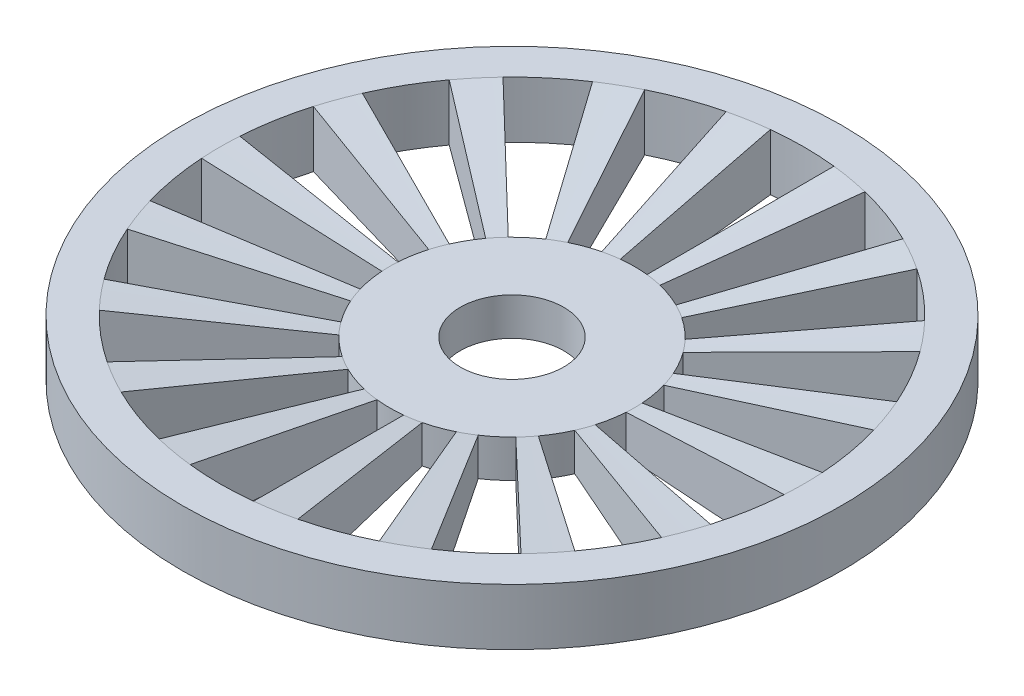
SolidWorks part; units mm, degrees
ref_plane "Front Plane" through (0, 0, 0) normal (0, 0, 1) x (1, 0, 0)
ref_plane "Top Plane" through (0, 0, 0) normal (0, 1, 0) x (1, 0, 0)
ref_plane "Right Plane" through (0, 0, 0) normal (1, 0, 0) x (0, 0, -1)
ref_plane "Plane1" through (0, 3, 0) normal (0, 1, 0) x (1, 0, 0)
sketch "Sketch1" plane through (0, 0, 0) normal (0, 1, 0) x (1, 0, 0)
  circle A0 centre (0, 0) radius 15.5
  circle A1 centre (0, 0) radius 17.5
  point P17 (14.8721, 4.3669)
  point P26 (13.0394, 8.3799)
  point P27 (10.1503, 11.7141)
  point P28 (6.4389, 14.0993)
  point P29 (2.2059, 15.3422)
  point P30 (-2.2059, 15.3422)
  point P31 (-6.4389, 14.0993)
  point P32 (-10.1503, 11.7141)
  point P33 (-13.0394, 8.3799)
  point P34 (-14.8721, 4.3669)
  point P35 (-15.5, 0)
  point P36 (-14.8721, -4.3669)
  point P37 (-13.0394, -8.3799)
  point P38 (-10.1503, -11.7141)
  point P39 (-6.4389, -14.0993)
  point P40 (-2.2059, -15.3422)
  point P41 (2.2059, -15.3422)
  point P42 (6.4389, -14.0993)
  point P43 (10.1503, -11.7141)
  point P44 (13.0394, -8.3799)
  point P45 (14.8721, -4.3669)
  point P46 (15.5, 0)
  dimension "D1" = 35
  dimension "D2" = 2
sketch "Sketch2" plane through (0, 0, 0) normal (0, 1, 0) x (1, 0, 0)
  circle A0 centre (0, 0) radius 6.5
  dimension "D1" = 13
sketch "Sketch4" plane through (0, 0, 0) normal (0, 1, 0) x (1, 0, 0)
  line L0 (0, 6.5) -> (0, 17.5) construction
  line L3 (1.1287, 6.4013) -> (3.0388, 17.2341) construction
  line L4 (2.2231, 6.108) -> (5.9854, 16.4446) construction
  line L5 (3.25, 5.6292) -> (8.75, 15.1554) construction
  line L6 (4.1781, 4.9793) -> (11.2488, 13.4058) construction
  line L7 (4.9793, 4.1781) -> (13.4058, 11.2488) construction
  line L8 (5.6292, 3.25) -> (15.1554, 8.75) construction
  line L9 (6.108, 2.2231) -> (16.4446, 5.9854) construction
  line L10 (6.4013, 1.1287) -> (17.2341, 3.0388) construction
  line L11 (6.5, 0) -> (17.5, 0) construction
  line L12 (6.4013, -1.1287) -> (17.2341, -3.0388) construction
  line L13 (6.108, -2.2231) -> (16.4446, -5.9854) construction
  line L14 (5.6292, -3.25) -> (15.1554, -8.75) construction
  line L15 (4.9793, -4.1781) -> (13.4058, -11.2488) construction
  line L16 (4.1781, -4.9793) -> (11.2488, -13.4058) construction
  line L17 (3.25, -5.6292) -> (8.75, -15.1554) construction
  line L18 (2.2231, -6.108) -> (5.9854, -16.4446) construction
  line L19 (1.1287, -6.4013) -> (3.0388, -17.2341) construction
  line L20 (0, -6.5) -> (0, -17.5) construction
  line L21 (-1.1287, -6.4013) -> (-3.0388, -17.2341) construction
  line L22 (-2.2231, -6.108) -> (-5.9854, -16.4446) construction
  line L23 (-3.25, -5.6292) -> (-8.75, -15.1554) construction
  line L24 (-4.1781, -4.9793) -> (-11.2488, -13.4058) construction
  line L25 (-4.9793, -4.1781) -> (-13.4058, -11.2488) construction
  line L26 (-5.6292, -3.25) -> (-15.1554, -8.75) construction
  line L27 (-6.108, -2.2231) -> (-16.4446, -5.9854) construction
  line L28 (-6.4013, -1.1287) -> (-17.2341, -3.0388) construction
  line L29 (-6.5, 0) -> (-17.5, 0) construction
  line L30 (-6.4013, 1.1287) -> (-17.2341, 3.0388) construction
  line L31 (-6.108, 2.2231) -> (-16.4446, 5.9854) construction
  line L32 (-5.6292, 3.25) -> (-15.1554, 8.75) construction
  line L33 (-4.9793, 4.1781) -> (-13.4058, 11.2488) construction
  line L34 (-4.1781, 4.9793) -> (-11.2488, 13.4058) construction
  line L35 (-3.25, 5.6292) -> (-8.75, 15.1554) construction
  line L36 (-2.2231, 6.108) -> (-5.9854, 16.4446) construction
  line L37 (-1.1287, 6.4013) -> (-3.0388, 17.2341) construction
  line L39 (0.7076, 6.4614) -> (1.9052, 17.396)
  line L42 (1.545, 6.3137) -> (4.1595, 16.9985)
  line L43 (2.8749, 5.8297) -> (7.7401, 15.6953)
  line L44 (3.6112, 5.4046) -> (9.7225, 14.5507)
  line L45 (4.6954, 4.4948) -> (12.6414, 12.1015)
  line L46 (5.2419, 3.8435) -> (14.1128, 10.3479)
  line L47 (5.9495, 2.6179) -> (16.018, 7.0481)
  line L48 (6.2403, 1.8189) -> (16.8009, 4.897)
  line L49 (6.4861, 0.4251) -> (17.4625, 1.1446)
  line L50 (6.4861, -0.4251) -> (17.4625, -1.1446)
  line L51 (6.2403, -1.8189) -> (16.8009, -4.897)
  line L52 (5.9495, -2.6179) -> (16.018, -7.0481)
  line L53 (5.2419, -3.8435) -> (14.1128, -10.3479)
  line L54 (4.6954, -4.4948) -> (12.6414, -12.1015)
  line L55 (3.6112, -5.4046) -> (9.7225, -14.5507)
  line L56 (2.8749, -5.8297) -> (7.7401, -15.6953)
  line L57 (1.545, -6.3137) -> (4.1595, -16.9985)
  line L58 (0.7076, -6.4614) -> (1.9052, -17.396)
  line L59 (-0.7076, -6.4614) -> (-1.9052, -17.396)
  line L60 (-1.545, -6.3137) -> (-4.1595, -16.9985)
  line L61 (-2.8749, -5.8297) -> (-7.7401, -15.6953)
  line L62 (-3.6112, -5.4046) -> (-9.7225, -14.5507)
  line L63 (-4.6954, -4.4948) -> (-12.6414, -12.1015)
  line L64 (-5.2419, -3.8435) -> (-14.1128, -10.3479)
  line L65 (-5.9495, -2.6179) -> (-16.018, -7.0481)
  line L66 (-6.2403, -1.8189) -> (-16.8009, -4.897)
  line L67 (-6.4861, -0.4251) -> (-17.4625, -1.1446)
  line L68 (-6.4861, 0.4251) -> (-17.4625, 1.1446)
  line L69 (-6.2403, 1.8189) -> (-16.8009, 4.897)
  line L70 (-5.9495, 2.6179) -> (-16.018, 7.0481)
  line L71 (-5.2419, 3.8435) -> (-14.1128, 10.3479)
  line L72 (-4.6954, 4.4948) -> (-12.6414, 12.1015)
  line L73 (-3.6112, 5.4046) -> (-9.7225, 14.5507)
  line L74 (-2.8749, 5.8297) -> (-7.7401, 15.6953)
  line L75 (-1.545, 6.3137) -> (-4.1595, 16.9985)
  line L76 (-0.7076, 6.4614) -> (-1.9052, 17.396)
  circle A86 centre (0, 0) radius 6.5 construction
  circle A90 centre (0, 0) radius 17.5 construction
  arc A91 (0.7076, 6.4614) -> (1.545, 6.3137) centre (0, 0) cw
  arc A92 (4.1595, 16.9985) -> (1.9052, 17.396) centre (0, 0) ccw
  arc A93 (9.7225, 14.5507) -> (7.7401, 15.6953) centre (0, 0) ccw
  arc A94 (2.8749, 5.8297) -> (3.6112, 5.4046) centre (0, 0) cw
  arc A95 (14.1128, 10.3479) -> (12.6414, 12.1015) centre (0, 0) ccw
  arc A96 (4.6954, 4.4948) -> (5.2419, 3.8435) centre (0, 0) cw
  arc A97 (16.8009, 4.897) -> (16.018, 7.0481) centre (0, 0) ccw
  arc A98 (5.9495, 2.6179) -> (6.2403, 1.8189) centre (0, 0) cw
  arc A99 (17.4625, -1.1446) -> (17.4625, 1.1446) centre (0, 0) ccw
  arc A100 (6.4861, 0.4251) -> (6.4861, -0.4251) centre (0, 0) cw
  arc A101 (16.018, -7.0481) -> (16.8009, -4.897) centre (0, 0) ccw
  arc A102 (6.2403, -1.8189) -> (5.9495, -2.6179) centre (0, 0) cw
  arc A103 (12.6414, -12.1015) -> (14.1128, -10.3479) centre (0, 0) ccw
  arc A104 (5.2419, -3.8435) -> (4.6954, -4.4948) centre (0, 0) cw
  arc A105 (7.7401, -15.6953) -> (9.7225, -14.5507) centre (0, 0) ccw
  arc A106 (3.6112, -5.4046) -> (2.8749, -5.8297) centre (0, 0) cw
  arc A107 (1.9052, -17.396) -> (4.1595, -16.9985) centre (0, 0) ccw
  arc A108 (1.545, -6.3137) -> (0.7076, -6.4614) centre (0, 0) cw
  arc A109 (-4.1595, -16.9985) -> (-1.9052, -17.396) centre (0, 0) ccw
  arc A110 (-0.7076, -6.4614) -> (-1.545, -6.3137) centre (0, 0) cw
  arc A111 (-9.7225, -14.5507) -> (-7.7401, -15.6953) centre (0, 0) ccw
  arc A112 (-2.8749, -5.8297) -> (-3.6112, -5.4046) centre (0, 0) cw
  arc A113 (-14.1128, -10.3479) -> (-12.6414, -12.1015) centre (0, 0) ccw
  arc A114 (-4.6954, -4.4948) -> (-5.2419, -3.8435) centre (0, 0) cw
  arc A115 (-16.8009, -4.897) -> (-16.018, -7.0481) centre (0, 0) ccw
  arc A116 (-5.9495, -2.6179) -> (-6.2403, -1.8189) centre (0, 0) cw
  arc A117 (-17.4625, 1.1446) -> (-17.4625, -1.1446) centre (0, 0) ccw
  arc A118 (-6.4861, -0.4251) -> (-6.4861, 0.4251) centre (0, 0) cw
  arc A119 (-16.018, 7.0481) -> (-16.8009, 4.897) centre (0, 0) ccw
  arc A120 (-6.2403, 1.8189) -> (-5.9495, 2.6179) centre (0, 0) cw
  arc A121 (-12.6414, 12.1015) -> (-14.1128, 10.3479) centre (0, 0) ccw
  arc A122 (-5.2419, 3.8435) -> (-4.6954, 4.4948) centre (0, 0) cw
  arc A123 (-7.7401, 15.6953) -> (-9.7225, 14.5507) centre (0, 0) ccw
  arc A124 (-3.6112, 5.4046) -> (-2.8749, 5.8297) centre (0, 0) cw
  arc A125 (-1.9052, 17.396) -> (-4.1595, 16.9985) centre (0, 0) ccw
  arc A126 (-1.545, 6.3137) -> (-0.7076, 6.4614) centre (0, 0) cw
  point P49 (0, 0)
  point P80 (0, 0)
  point P153 (0, 0)
  point P188 (0, 0)
  dimension "D2" = 35
  dimension "D3" = 13
  dimension "D5" = 7.5
  dimension "D6" = 12.5
  dimension "D1" = 36
  dimension "D4" = 18
extrude "Boss-Extrude1" add sketch "Sketch1" along normal up to surface (3 mm away) up to plane "Plane1"
extrude "Boss-Extrude2" add sketch "Sketch2" along normal blind 2 separate body
extrude "Boss-Extrude3" add sketch "Sketch4" along normal up to surface (3 mm away) up to plane "Plane1"
sketch "Sketch6" plane through (0, 0, 0) normal (0, 0, 1) x (1, 0, 0)
  line L0 (0, -983.4456) -> (0, 49016.5544) construction
sketch "Sketch7" plane through (0, 0, 0) normal (1, 0, 0) x (0, 0, -1)
  line L0 (6.5, 2) -> (15.5, 3)
  line L2 (15.5, 3) -> (6.5, 3)
  line L3 (6.5, 3) -> (6.5, 2)
  line L4 (6.4614, 2) -> (6.3137, 2) construction
  line L5 (6.5, 2) -> (6.4614, 2) construction
  point P2 (0, 0)
  point P3 (0, 0)
  point P10 (0, 0)
  point P11 (0, 0)
revolve "Cut-Revolve1" cut sketch "Sketch7" angle 360 about L0
sketch "Sketch8" plane through (0, 2, 0) normal (0, 1, 0) x (1, 0, 0)
  circle A0 centre (0, 0) radius 2.75
  dimension "D1" = 5.5
extrude "Cut-Extrude1" cut sketch "Sketch8" against normal through all
sketch "Sketch9" plane through (0, 0, 0) normal (0, -1, 0) x (1, 0, 0)
  line L1 (-4.35, 4.35) -> (4.35, 4.35)
  line L2 (-4.35, 4.35) -> (-4.35, -4.35)
  line L3 (-4.35, -4.35) -> (4.35, -4.35)
  line L4 (4.35, 4.35) -> (4.35, -4.35)
  line L5 (-4.35, 4.35) -> (4.35, -4.35) construction
  line L6 (-4.35, -4.35) -> (4.35, 4.35) construction
  circle A1 centre (0, 0) radius 6.5 construction
  circle A2 centre (0, 0) radius 6.5
  dimension "D1" = 8.7
